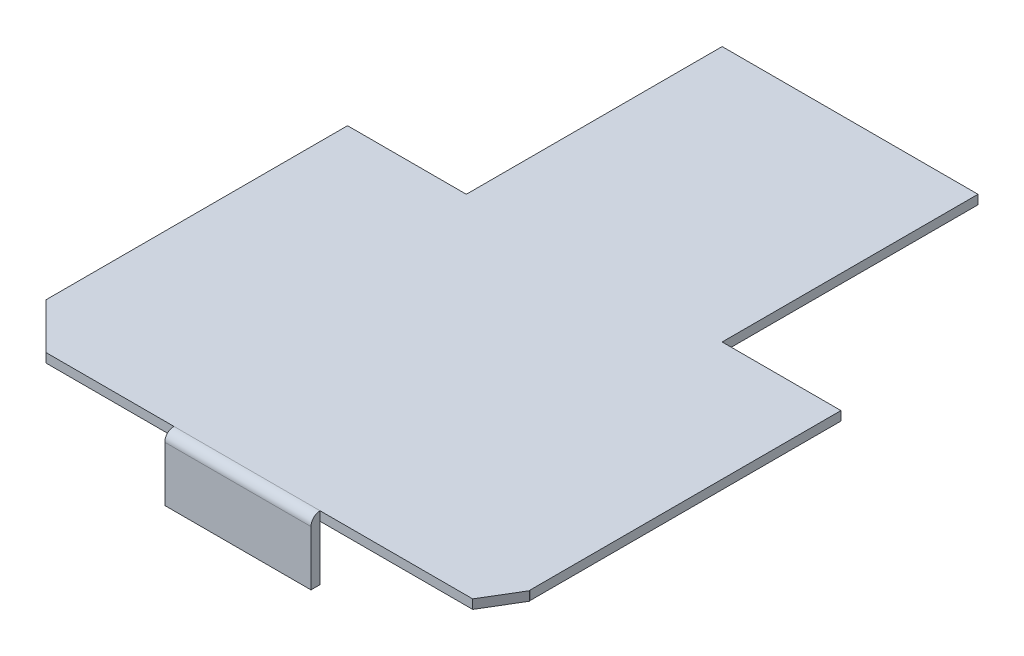
SolidWorks part; units mm, degrees
ref_plane "Front Plane" through (0, 0, 0) normal (0, 0, 1) x (1, 0, 0)
ref_plane "Top Plane" through (0, 0, 0) normal (0, 1, 0) x (1, 0, 0)
ref_plane "Right Plane" through (0, 0, 0) normal (1, 0, 0) x (0, 0, -1)
sketch "Sketch1" plane through (0, 0, 0) normal (0, 1, 0) x (1, 0, 0)
  line L1 (-85.725, -53.975) -> (85.725, -53.975)
  line L2 (-85.725, -53.975) -> (-85.725, 53.975)
  line L3 (-85.725, 53.975) -> (85.725, 53.975)
  line L4 (85.725, -53.975) -> (85.725, 53.975)
  line L5 (-85.725, -53.975) -> (85.725, 53.975) construction
  line L6 (-85.725, 53.975) -> (85.725, -53.975) construction
  point P0 (0, 0)
  dimension "D1" = 107.95
  dimension "D2" = 171.45
extrude "Boss-Extrude1" add sketch "Sketch1" along normal blind 3.175
sketch "Sketch2" plane through (0, 3.175, 0) normal (0, 1, 0) x (1, 0, 0)
  line L0 (-85.725, -53.975) -> (-82.55, -66.675)
  line L1 (-82.55, -66.675) -> (88.9, -66.675)
  line L2 (88.9, -66.675) -> (85.725, -53.975)
  line L3 (85.725, -53.975) -> (-85.725, -53.975)
  dimension "D1" = 12.7
extrude "Boss-Extrude2" add sketch "Sketch2" against normal blind 3.175
sketch "Sketch4" plane through (0, 0, 0) normal (0, -1, 0) x (1, 0, 0)
  line L1 (-82.55, 66.675) -> (88.9, 66.675) construction
  line L3 (-25.4, 66.675) -> (25.4, 66.675)
  line L4 (-25.4, 66.675) -> (-25.4, 69.85)
  line L5 (-25.4, 69.85) -> (25.4, 69.85)
  line L6 (25.4, 66.675) -> (25.4, 69.85)
  dimension "D1" = 3.175
extrude "Boss-Extrude3" add sketch "Sketch4" along normal blind 19.05
chamfer "Chamfer1" distance 12.7 angle 45 2 edges at (88.9, 1.5875, 66.675) (-82.55, 1.5875, 66.675)
sketch "Sketch6" plane through (0, 3.175, 0) normal (0, 1, 0) x (1, 0, 0)
  line L0 (85.725, 53.975) -> (-85.725, 53.975) construction
  line L1 (-44.45, 53.975) -> (44.45, 53.975)
  line L2 (-44.45, 53.975) -> (-44.45, 142.875)
  line L3 (-44.45, 142.875) -> (44.45, 142.875)
  line L4 (44.45, 53.975) -> (44.45, 142.875)
  line L5 (0, 0) -> (0, 152.4) construction
  dimension "D1" = 88.9
  dimension "D2" = 88.9
  dimension "D3" = 44.45
  dimension "D4" = 152.4
extrude "Boss-Extrude4" add sketch "Sketch6" against normal blind 3.175
sketch "Sketch10" plane through (25.4, 0, 0) normal (1, 0, 0) x (0, 0, -1)
  line L0 (-66.675, 3.175) -> (-66.675, 0)
  line L1 (-66.675, 0) -> (-69.85, 0)
  arc A0 (-69.85, 0) -> (-66.675, 3.175) centre (-66.675, 0) cw
extrude "Boss-Extrude7" add sketch "Sketch10" against normal blind 50.8
